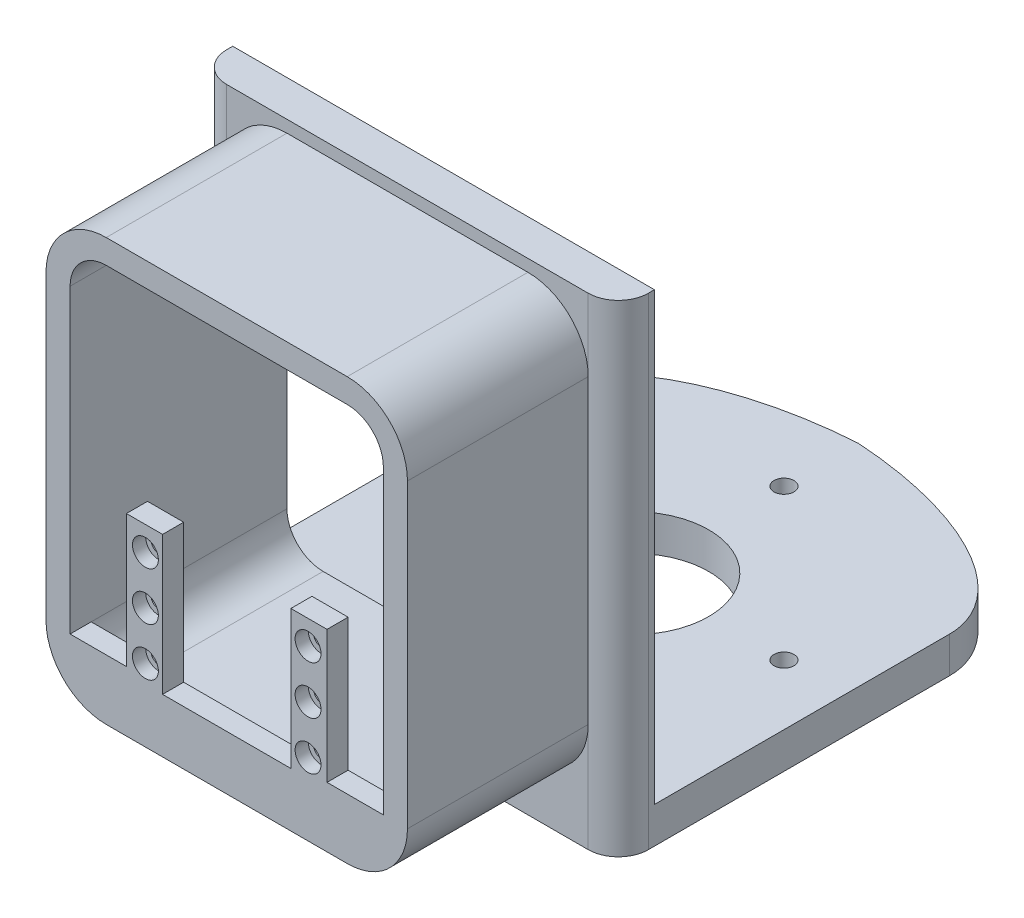
SolidWorks part; units mm, degrees
ref_plane "Front Plane" through (0, 0, 0) normal (0, 0, 1) x (1, 0, 0)
ref_plane "Top Plane" through (0, 0, 0) normal (0, 1, 0) x (1, 0, 0)
ref_plane "Right Plane" through (0, 0, 0) normal (1, 0, 0) x (0, 0, -1)
sketch "Sketch1" plane through (0, 0, 0) normal (0, 0, 1) x (1, 0, 0)
  line L1 (-20, -35) -> (20, -35)
  line L2 (-30, -25) -> (-30, 25)
  line L3 (-20, 35) -> (20, 35)
  line L4 (30, -25) -> (30, 25)
  line L5 (-30, -35) -> (30, 35) construction
  line L6 (-30, 35) -> (30, -35) construction
  arc A1 (20, 35) -> (30, 25) centre (20, 25) cw
  arc A2 (20, -35) -> (30, -25) centre (20, -25) ccw
  arc A3 (-20, -35) -> (-30, -25) centre (-20, -25) cw
  arc A4 (-30, 25) -> (-20, 35) centre (-20, 25) cw
  point P0 (0, 0)
  dimension "D1" = 60
  dimension "D3" = 10
  dimension "D2" = 70
extrude "Boss-Extrude1" add sketch "Sketch1" against normal blind 30
ref_plane "Plane1" through (60, 0, 0) normal (1, 0, 0) x (0, 0, -1)
ref_plane "Plane2" through (60, 0, 0) normal (1, 0, 0) x (0, 0, -1)
sketch "Sketch10" plane through (0, 0, -30) normal (0, 0, -1) x (-1, 0, 0)
  line L0 (0, -3) -> (0, 0) construction
  line L1 (-35, -43) -> (35, -43)
  line L2 (-35, -43) -> (-35, 37)
  line L3 (-35, 37) -> (35, 37)
  line L4 (35, -43) -> (35, 37)
  line L5 (-35, -43) -> (35, 37) construction
  line L6 (-35, 37) -> (35, -43) construction
  point P0 (0, -3)
  dimension "D3" = 3
  dimension "D1" = 80
  dimension "D2" = 70
extrude "Boss-Extrude6" add sketch "Sketch10" along normal blind 75
sketch "Sketch14" plane through (0, 0, 0) normal (0, 0, 1) x (1, 0, 0)
  line L8 (20, 31) -> (-20, 31)
  line L9 (26, -25) -> (26, 25)
  line L10 (-20, -31) -> (20, -31)
  line L11 (-26, 25) -> (-26, -25)
  line L12 (20, 31) -> (-20, 31)
  line L13 (26, -25) -> (26, 25)
  line L14 (-20, -31) -> (20, -31)
  line L15 (-26, 25) -> (-26, -25)
  arc A10 (26, 25) -> (20, 31) centre (20, 25) ccw
  arc A11 (20, -31) -> (26, -25) centre (20, -25) ccw
  arc A12 (-26, -25) -> (-20, -31) centre (-20, -25) ccw
  arc A13 (-20, 31) -> (-26, 25) centre (-20, 25) ccw
  arc A14 (26, 25) -> (20, 31) centre (20, 25) ccw
  arc A15 (20, -31) -> (26, -25) centre (20, -25) ccw
  arc A16 (-26, -25) -> (-20, -31) centre (-20, -25) ccw
  arc A17 (-20, 31) -> (-26, 25) centre (-20, 25) ccw
  dimension "D1" = 4
extrude "Cut-Extrude7" cut sketch "Sketch14" against normal blind 46
sketch "Sketch15" plane through (0, 0, 0) normal (0, 0, 1) x (1, 0, 0)
  line L0 (0, 0) -> (0, -17.9719) construction
  line L1 (-16.65, -3) -> (-10.65, -3)
  line L2 (-10.65, -3) -> (-10.65, -26)
  line L3 (-10.65, -26) -> (10.65, -26)
  line L4 (10.65, -26) -> (10.65, -3)
  line L5 (10.65, -3) -> (16.65, -3)
  line L6 (16.65, -3) -> (16.65, -25)
  line L8 (-16.65, -3) -> (-16.65, -25)
  line L10 (0, 0) -> (13.5, 0) construction
  line L11 (13.5, 0) -> (13.5, -7) construction
  line L12 (13.5, -7) -> (13.5, -15) construction
  line L13 (13.5, -15) -> (13.5, -23) construction
  line L14 (-20, -31) -> (20, -31) construction
  line L15 (-20, -31) -> (20, -31)
  line L16 (26, -25) -> (16.65, -25)
  line L17 (-26, -25) -> (-16.65, -25)
  circle A0 centre (0, 0) radius 11 construction
  circle A1 centre (13.5, -7) radius 1.25
  circle A3 centre (13.5, -15) radius 1.25
  circle A4 centre (13.5, -23) radius 1.25
  circle A5 centre (-13.5, -7) radius 1.25
  circle A6 centre (-13.5, -15) radius 1.25
  circle A7 centre (-13.5, -23) radius 1.25
  arc A9 (-26, -25) -> (-20, -31) centre (-20, -25) ccw
  arc A10 (26, -25) -> (20, -31) centre (20, -25) cw
  point P5 (0, -26)
  dimension "D1" = 22
  dimension "D5" = 2.5
  dimension "D2" = 21.3
  dimension "D3" = 13.5
  dimension "D4" = 7
  dimension "D6" = 8
  dimension "D7" = 8
  dimension "D8" = 6
  dimension "D9" = 5
  dimension "D10" = 3
extrude "Boss-Extrude7" add sketch "Sketch15" against normal blind 3.5
sketch "Sketch17" plane through (0, 0, 0) normal (0, 0, 1) x (1, 0, 0)
  circle A0 centre (-13.5, -7) radius 2.15
  circle A1 centre (-13.5, -15) radius 2.15
  circle A2 centre (-13.5, -23) radius 2.15
  circle A3 centre (13.5, -7) radius 2.15
  circle A4 centre (13.5, -15) radius 2.15
  circle A5 centre (13.5, -23) radius 2.15
  dimension "D1" = 4.3
extrude "Cut-Extrude9" cut sketch "Sketch17" against normal blind 2.2
sketch "Sketch19" plane through (35, 0, 0) normal (1, 0, 0) x (0, 0, -1)
  line L0 (105, -43) -> (30, -43) construction
  line L1 (105, 37) -> (36, 37)
  line L2 (105, 37) -> (105, -37)
  line L3 (105, -37) -> (36, -37)
  line L4 (36, 37) -> (36, -37)
  line L5 (30, 37) -> (30, -43) construction
  dimension "D1" = 6
  dimension "D2" = 6
extrude "Cut-Extrude11" cut sketch "Sketch19" against normal blind 70
sketch "Sketch20" plane through (0, -43, 0) normal (0, -1, 0) x (1, 0, 0)
  line L0 (-35, -30) -> (35, -105) construction
  line L1 (25, -67.5) -> (0, -67.5) construction
  circle A0 centre (25, -67.5) radius 1.65
  circle A1 centre (0, -92.5) radius 1.65
  circle A2 centre (-25, -67.5) radius 1.65
  circle A3 centre (0, -42.5) radius 1.65
  point P6 (0, -67.5)
  point P16 (0, -67.5)
  dimension "D1" = 3.3
  dimension "D3" = 25
  dimension "D2" = 4
extrude "Cut-Extrude12" cut sketch "Sketch20" against normal blind 10
sketch "Sketch21" plane through (0, -37, 0) normal (0, 1, 0) x (1, 0, 0)
  line L0 (-25, 67.5) -> (25, 67.5) construction
  circle A0 centre (0, 67.5) radius 12.5
  point P6 (0, 67.5)
  dimension "D1" = 25
extrude "Cut-Extrude13" cut sketch "Sketch21" against normal blind 10
fillet "Fillet2" radius 20 2 edges at (35, -40, -105) (-35, -40, -105) second distance 40 first distance on face at (35, -14.3333, -57) first distance on face at (-35, -14.3333, -57)
fillet "Fillet4" radius 5 2 edges at (35, -3, -30) (-35, -3, -30)
